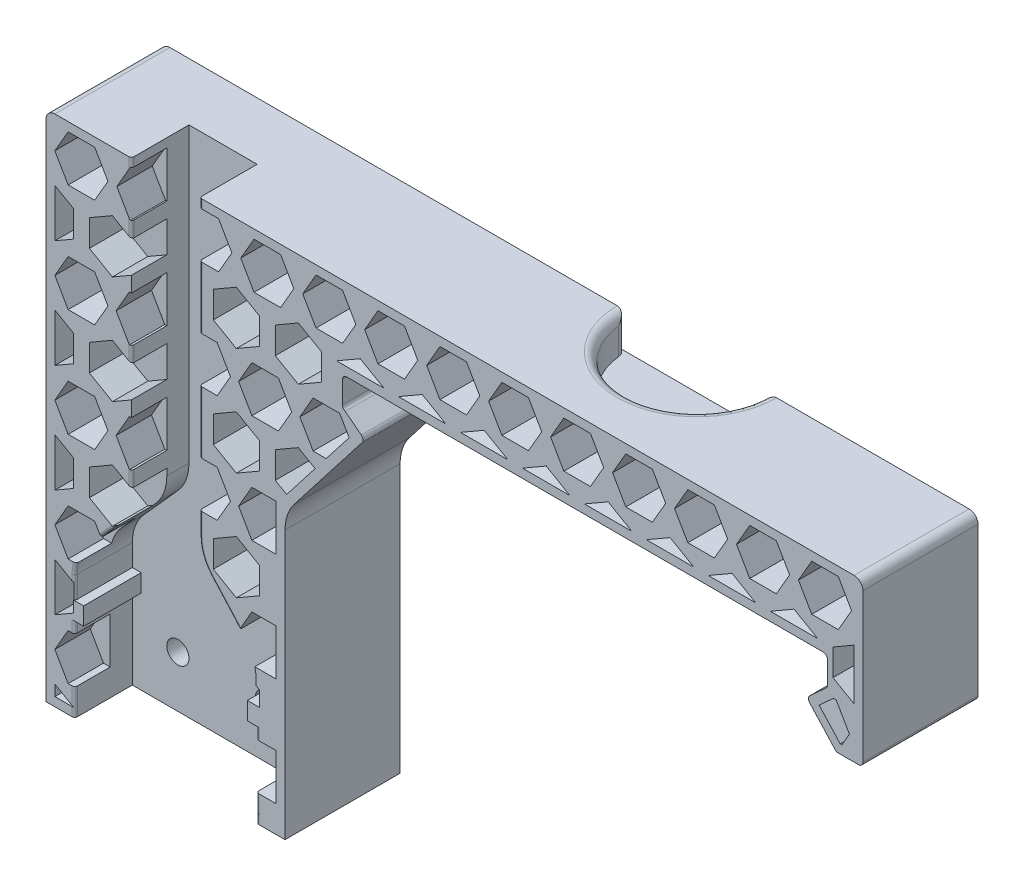
SolidWorks part; units mm, degrees
ref_plane "Front Plane" through (0, 0, 0) normal (0, 0, 1) x (1, 0, 0)
ref_plane "Top Plane" through (0, 0, 0) normal (0, 1, 0) x (1, 0, 0)
ref_plane "Right Plane" through (0, 0, 0) normal (1, 0, 0) x (0, 0, -1)
sketch "Sketch1" plane through (0, 0, 0) normal (0, 0, 1) x (1, 0, 0)
  line L0 (-19.1592, 3.1319) -> (34.6408, 3.1319)
  line L1 (-38.1408, 12.3758) -> (38.1408, 12.3758)
  line L4 (39.1408, 11.3758) -> (39.1408, -5.3957)
  line L5 (-53.1408, 0) -> (55.5927, 0) construction
  line L7 (35.1408, 2.6319) -> (35.1408, 0.1519)
  line L8 (34.9786, -0.2167) -> (33.1502, -1.8923)
  line L9 (-19.6592, 2.6319) -> (-19.6592, 0.1519)
  line L10 (-19.3447, -0.3124) -> (-17.527, -1.7246)
  line L12 (-17.1322, 5.631) -> (-17.1322, -19.9261) construction
  line L13 (-11.8322, 5.631) -> (-11.8322, -19.9261) construction
  line L14 (-19.6592, 23.1234) -> (-19.6592, -22.8153) construction
  line L16 (35.1408, 17.1234) -> (35.1408, -28.8153) construction
  line L17 (33.1194, -2.5987) -> (35.9922, -5.7336)
  line L18 (36.3608, -5.8957) -> (38.6408, -5.8957)
  line L19 (-17.4389, -2.4262) -> (-25.0892, -12.2733)
  line L20 (0, 22.1727) -> (0, -33.9968) construction
  line L21 (-85.6654, -9.6242) -> (72.0343, -9.6242) construction
  line L23 (-50.1408, -45.6242) -> (-26.1408, -45.6242)
  line L24 (-26.1408, -45.6242) -> (-26.1408, -15.3409)
  line L25 (-38.1408, 12.3758) -> (-52.1408, 12.3758)
  line L26 (-148.4921, -45.6242) -> (55.8577, -45.6242) construction
  line L27 (-53.1408, 11.3758) -> (-53.1408, -45.6242)
  line L28 (-53.1408, -45.6242) -> (-50.1408, -45.6242)
  line L30 (-39.6408, -25.8208) -> (-39.6408, -60.1482) construction
  arc A5 (-19.3447, -0.3124) -> (-19.6592, 0.1519) centre (-19.1592, 0.1519) cw
  arc A6 (35.1408, 0.1519) -> (34.9786, -0.2167) centre (34.6408, 0.1519) cw
  arc A7 (-19.1592, 3.1319) -> (-19.6592, 2.6319) centre (-19.1592, 2.6319) ccw
  arc A8 (35.1408, 2.6319) -> (34.6408, 3.1319) centre (34.6408, 2.6319) ccw
  arc A10 (38.6408, -5.8957) -> (39.1408, -5.3957) centre (38.6408, -5.3957) ccw
  arc A11 (36.3608, -5.8957) -> (35.9922, -5.7336) centre (36.3608, -5.3957) cw
  arc A12 (33.1194, -2.5987) -> (33.1502, -1.8923) centre (33.488, -2.2609) cw
  arc A13 (-17.4389, -2.4262) -> (-17.527, -1.7246) centre (-17.8338, -2.1194) ccw
  arc A14 (39.1408, 11.3758) -> (38.1408, 12.3758) centre (38.1408, 11.3758) ccw
  arc A15 (-52.1408, 12.3758) -> (-53.1408, 11.3758) centre (-52.1408, 11.3758) ccw
  arc A16 (-26.1408, -15.3409) -> (-25.0892, -12.2733) centre (-21.1408, -15.3409) cw
  point P0 (0, 0)
  point P1 (0, 12.3758)
  point P20 (-19.6592, -10.5)
  point P28 (-17.1322, -2.0313)
  point P29 (24.1408, -9.6242)
  point P33 (32.7816, -2.2301)
  point P36 (-19.6592, -0.0681)
  point P39 (35.1408, -0.0681)
  point P42 (-19.6592, 3.1319)
  point P45 (35.1408, 3.1319)
  point P49 (39.1408, -5.8957)
  point P52 (36.1408, -5.8957)
  point P55 (32.7816, -2.2301)
  point P58 (-17.1322, -2.0313)
  dimension "D8" = 90
  dimension "D13" = 3
  dimension "D15" = 90
  dimension "D16" = 4.9721
  dimension "D17" = 0.5
  dimension "D18" = 5.631
  dimension "D21" = 1
  dimension "D22" = 1
  dimension "D5" = 5
  dimension "D1" = 54.8
  dimension "D2" = 3.2
  dimension "D3" = 3.2
  dimension "D4" = 22
  dimension "D6" = 3.2
  dimension "D7" = 3.2
  dimension "D9" = 5.3
  dimension "D10" = 58
  dimension "D11" = 27
  dimension "D12" = 92.2816
  dimension "D14" = 4
  dimension "D19" = 19.9261
  dimension "D23" = 2.3018
extrude "Boss-Extrude1" add sketch "Sketch1" along normal mid plane 13
sketch "Sketch2" plane through (0, 0, 6.5) normal (0, 0, 1) x (1, 0, 0)
  line L0 (-53.1408, 11.3758) -> (-53.1408, -45.6242) construction
  line L1 (-49.1408, 18.485) -> (-49.1408, -51.4128) construction
  line L2 (-47.6408, -6.0165) -> (-46.1408, -3.4185)
  line L3 (-47.6408, 6.1796) -> (-46.1408, 8.7777)
  line L4 (-46.1408, 8.7777) -> (-47.6408, 11.3758)
  line L5 (-47.6408, 11.3758) -> (-50.6408, 11.3758)
  line L6 (-50.6408, 11.3758) -> (-52.1408, 8.7777)
  line L7 (-52.1408, 8.7777) -> (-50.6408, 6.1796)
  line L8 (-50.6408, 6.1796) -> (-47.6408, 6.1796)
  line L9 (38.1408, 12.3758) -> (-52.1408, 12.3758) construction
  line L10 (-40.6408, 6.1796) -> (-39.1408, 8.7777)
  line L11 (-39.1408, 8.7777) -> (-40.6408, 11.3758)
  line L12 (-40.6408, 11.3758) -> (-43.6408, 11.3758)
  line L13 (-43.6408, 11.3758) -> (-45.1408, 8.7777)
  line L14 (-45.1408, 8.7777) -> (-43.6408, 6.1796)
  line L15 (-43.6408, 6.1796) -> (-40.6408, 6.1796)
  line L16 (-33.6408, 6.1796) -> (-32.1408, 8.7777)
  line L17 (-32.1408, 8.7777) -> (-33.6408, 11.3758)
  line L18 (-33.6408, 11.3758) -> (-36.6408, 11.3758)
  line L19 (-36.6408, 11.3758) -> (-38.1408, 8.7777)
  line L20 (-38.1408, 8.7777) -> (-36.6408, 6.1796)
  line L21 (-36.6408, 6.1796) -> (-33.6408, 6.1796)
  line L22 (-26.6408, 6.1796) -> (-25.1408, 8.7777)
  line L23 (-25.1408, 8.7777) -> (-26.6408, 11.3758)
  line L24 (-26.6408, 11.3758) -> (-29.6408, 11.3758)
  line L25 (-29.6408, 11.3758) -> (-31.1408, 8.7777)
  line L26 (-31.1408, 8.7777) -> (-29.6408, 6.1796)
  line L27 (-29.6408, 6.1796) -> (-26.6408, 6.1796)
  line L28 (-19.6408, 6.1796) -> (-18.1408, 8.7777)
  line L29 (-18.1408, 8.7777) -> (-19.6408, 11.3758)
  line L30 (-19.6408, 11.3758) -> (-22.6408, 11.3758)
  line L31 (-22.6408, 11.3758) -> (-24.1408, 8.7777)
  line L32 (-24.1408, 8.7777) -> (-22.6408, 6.1796)
  line L33 (-22.6408, 6.1796) -> (-19.6408, 6.1796)
  line L34 (-12.6408, 6.1796) -> (-11.1408, 8.7777)
  line L35 (-11.1408, 8.7777) -> (-12.6408, 11.3758)
  line L36 (-12.6408, 11.3758) -> (-15.6408, 11.3758)
  line L37 (-15.6408, 11.3758) -> (-17.1408, 8.7777)
  line L38 (-17.1408, 8.7777) -> (-15.6408, 6.1796)
  line L39 (-15.6408, 6.1796) -> (-12.6408, 6.1796)
  line L40 (-5.6408, 6.1796) -> (-4.1408, 8.7777)
  line L41 (-4.1408, 8.7777) -> (-5.6408, 11.3758)
  line L42 (-5.6408, 11.3758) -> (-8.6408, 11.3758)
  line L43 (-8.6408, 11.3758) -> (-10.1408, 8.7777)
  line L44 (-10.1408, 8.7777) -> (-8.6408, 6.1796)
  line L45 (-8.6408, 6.1796) -> (-5.6408, 6.1796)
  line L46 (1.3592, 6.1796) -> (2.8592, 8.7777)
  line L47 (2.8592, 8.7777) -> (1.3592, 11.3758)
  line L48 (1.3592, 11.3758) -> (-1.6408, 11.3758)
  line L49 (-1.6408, 11.3758) -> (-3.1408, 8.7777)
  line L50 (-3.1408, 8.7777) -> (-1.6408, 6.1796)
  line L51 (-1.6408, 6.1796) -> (1.3592, 6.1796)
  line L52 (8.3592, 6.1796) -> (9.8592, 8.7777)
  line L53 (9.8592, 8.7777) -> (8.3592, 11.3758)
  line L54 (8.3592, 11.3758) -> (5.3592, 11.3758)
  line L55 (5.3592, 11.3758) -> (3.8592, 8.7777)
  line L56 (3.8592, 8.7777) -> (5.3592, 6.1796)
  line L57 (5.3592, 6.1796) -> (8.3592, 6.1796)
  line L58 (15.3592, 6.1796) -> (16.8592, 8.7777)
  line L59 (16.8592, 8.7777) -> (15.3592, 11.3758)
  line L60 (15.3592, 11.3758) -> (12.3592, 11.3758)
  line L61 (12.3592, 11.3758) -> (10.8592, 8.7777)
  line L62 (10.8592, 8.7777) -> (12.3592, 6.1796)
  line L63 (12.3592, 6.1796) -> (15.3592, 6.1796)
  line L64 (22.3592, 6.1796) -> (23.8592, 8.7777)
  line L65 (23.8592, 8.7777) -> (22.3592, 11.3758)
  line L66 (22.3592, 11.3758) -> (19.3592, 11.3758)
  line L67 (19.3592, 11.3758) -> (17.8592, 8.7777)
  line L68 (17.8592, 8.7777) -> (19.3592, 6.1796)
  line L69 (19.3592, 6.1796) -> (22.3592, 6.1796)
  line L70 (29.3592, 6.1796) -> (30.8592, 8.7777)
  line L71 (30.8592, 8.7777) -> (29.3592, 11.3758)
  line L72 (29.3592, 11.3758) -> (26.3592, 11.3758)
  line L73 (26.3592, 11.3758) -> (24.8592, 8.7777)
  line L74 (24.8592, 8.7777) -> (26.3592, 6.1796)
  line L75 (26.3592, 6.1796) -> (29.3592, 6.1796)
  line L76 (36.3592, 6.1796) -> (37.8592, 8.7777)
  line L77 (37.8592, 8.7777) -> (36.3592, 11.3758)
  line L78 (36.3592, 11.3758) -> (33.3592, 11.3758)
  line L79 (33.3592, 11.3758) -> (31.8592, 8.7777)
  line L80 (31.8592, 8.7777) -> (33.3592, 6.1796)
  line L81 (33.3592, 6.1796) -> (36.3592, 6.1796)
  line L82 (-53.1408, -45.6242) -> (-26.1408, -45.6242) construction
  line L83 (-45.6408, 13.774) -> (-45.6408, 5.8279) construction
  line L84 (-43.0427, 1.1796) -> (-43.0427, 4.1796)
  line L85 (-43.0427, 4.1796) -> (-45.6408, 5.6796)
  line L86 (-45.6408, 5.6796) -> (-48.2389, 4.1796)
  line L87 (-48.2389, 4.1796) -> (-48.2389, 1.1796)
  line L88 (-48.2389, 1.1796) -> (-45.6408, -0.3204)
  line L89 (-45.6408, -0.3204) -> (-43.0427, 1.1796)
  line L90 (-50.0427, 1.1796) -> (-50.0427, 4.1796)
  line L91 (-50.0427, 4.1796) -> (-52.1408, 5.3909)
  line L95 (-52.1408, -0.0317) -> (-50.0427, 1.1796)
  line L96 (-36.0427, 1.1796) -> (-36.0427, 4.1796)
  line L97 (-36.0427, 4.1796) -> (-38.6408, 5.6796)
  line L98 (-38.6408, 5.6796) -> (-41.2389, 4.1796)
  line L99 (-41.2389, 4.1796) -> (-41.2389, 1.1796)
  line L100 (-41.2389, 1.1796) -> (-38.6408, -0.3204)
  line L101 (-38.6408, -0.3204) -> (-36.0427, 1.1796)
  line L102 (-29.0427, 1.1796) -> (-29.0427, 4.1796)
  line L103 (-29.0427, 4.1796) -> (-31.6408, 5.6796)
  line L104 (-31.6408, 5.6796) -> (-34.2389, 4.1796)
  line L105 (-34.2389, 4.1796) -> (-34.2389, 1.1796)
  line L106 (-34.2389, 1.1796) -> (-31.6408, -0.3204)
  line L107 (-31.6408, -0.3204) -> (-29.0427, 1.1796)
  line L108 (-22.0427, 1.1796) -> (-22.0427, 4.1796)
  line L109 (-22.0427, 4.1796) -> (-24.6408, 5.6796)
  line L110 (-24.6408, 5.6796) -> (-27.2389, 4.1796)
  line L111 (-27.2389, 4.1796) -> (-27.2389, 1.1796)
  line L112 (-27.2389, 1.1796) -> (-24.6408, -0.3204)
  line L113 (-24.6408, -0.3204) -> (-22.0427, 1.1796)
  line L114 (-15.0427, 4.1319) -> (-15.0427, 4.1796)
  line L115 (-15.0427, 4.1796) -> (-17.6408, 5.6796)
  line L116 (-17.6408, 5.6796) -> (-20.2389, 4.1796)
  line L117 (-20.2389, 4.1796) -> (-20.2389, 4.1319)
  line L120 (-8.0427, 4.1319) -> (-8.0427, 4.1796)
  line L121 (-8.0427, 4.1796) -> (-10.6408, 5.6796)
  line L122 (-10.6408, 5.6796) -> (-13.2389, 4.1796)
  line L123 (-13.2389, 4.1796) -> (-13.2389, 4.1319)
  line L126 (-1.0427, 4.1319) -> (-1.0427, 4.1796)
  line L127 (-1.0427, 4.1796) -> (-3.6408, 5.6796)
  line L128 (-3.6408, 5.6796) -> (-6.2389, 4.1796)
  line L129 (-6.2389, 4.1796) -> (-6.2389, 4.1319)
  line L132 (5.9573, 4.1319) -> (5.9573, 4.1796)
  line L133 (5.9573, 4.1796) -> (3.3592, 5.6796)
  line L134 (3.3592, 5.6796) -> (0.7611, 4.1796)
  line L135 (0.7611, 4.1796) -> (0.7611, 4.1319)
  line L138 (12.9573, 4.1319) -> (12.9573, 4.1796)
  line L139 (12.9573, 4.1796) -> (10.3592, 5.6796)
  line L140 (10.3592, 5.6796) -> (7.7611, 4.1796)
  line L141 (7.7611, 4.1796) -> (7.7611, 4.1319)
  line L144 (19.9573, 4.1319) -> (19.9573, 4.1796)
  line L145 (19.9573, 4.1796) -> (17.3592, 5.6796)
  line L146 (17.3592, 5.6796) -> (14.7611, 4.1796)
  line L147 (14.7611, 4.1796) -> (14.7611, 4.1319)
  line L150 (26.9573, 4.1319) -> (26.9573, 4.1796)
  line L151 (26.9573, 4.1796) -> (24.3592, 5.6796)
  line L152 (24.3592, 5.6796) -> (21.7611, 4.1796)
  line L153 (21.7611, 4.1796) -> (21.7611, 4.1319)
  line L156 (33.9573, 4.1319) -> (33.9573, 4.1796)
  line L157 (33.9573, 4.1796) -> (31.3592, 5.6796)
  line L158 (31.3592, 5.6796) -> (28.7611, 4.1796)
  line L159 (28.7611, 4.1796) -> (28.7611, 4.1319)
  line L164 (38.1408, 5.5535) -> (35.7611, 4.1796)
  line L165 (35.7611, 4.1796) -> (35.7611, 1.1796)
  line L166 (35.7611, 1.1796) -> (38.1408, -0.1943)
  line L180 (-52.1408, 38.7076) -> (-52.1408, -77.5427) construction
  line L181 (-52.1408, 5.3909) -> (-52.1408, -0.0317)
  line L182 (38.1408, 32.9327) -> (38.1408, -35.597) construction
  line L183 (39.1408, -5.3957) -> (39.1408, 11.3758) construction
  line L184 (-52.6408, 5.6796) -> (-55.2389, 4.1796) [skipped]
  line L185 (-55.2389, 4.1796) -> (-55.2389, 1.1796) [skipped]
  line L186 (-55.2389, 1.1796) -> (-52.6408, -0.3204) [skipped]
  line L187 (38.1408, 5.5535) -> (38.1408, -0.1943)
  line L188 (47.9573, 1.1796) -> (47.9573, 4.1796) [skipped]
  line L189 (47.9573, 4.1796) -> (45.3592, 5.6796) [skipped]
  line L190 (45.3592, 5.6796) -> (42.7611, 4.1796) [skipped]
  line L191 (42.7611, 4.1796) -> (42.7611, 1.1796) [skipped]
  line L192 (42.7611, 1.1796) -> (45.3592, -0.3204) [skipped]
  line L193 (45.3592, -0.3204) -> (47.9573, 1.1796) [skipped]
  line L194 (54.9573, 1.1796) -> (54.9573, 4.1796) [skipped]
  line L195 (54.9573, 4.1796) -> (52.3592, 5.6796) [skipped]
  line L196 (52.3592, 5.6796) -> (49.7611, 4.1796) [skipped]
  line L197 (49.7611, 4.1796) -> (49.7611, 1.1796) [skipped]
  line L198 (49.7611, 1.1796) -> (52.3592, -0.3204) [skipped]
  line L199 (52.3592, -0.3204) -> (54.9573, 1.1796) [skipped]
  line L200 (-73.3307, 4.1319) -> (58.1866, 4.1319) construction
  line L201 (40.9573, 4.1796) -> (38.3592, 5.6796) [skipped]
  line L202 (40.9573, 1.1796) -> (40.9573, 4.1796) [skipped]
  line L203 (38.3592, -0.3204) -> (40.9573, 1.1796) [skipped]
  line L204 (-19.1592, 3.1319) -> (34.6408, 3.1319) construction
  line L205 (-20.2389, 4.1319) -> (-15.0427, 4.1319)
  line L206 (-13.2389, 4.1319) -> (-8.0427, 4.1319)
  line L207 (-6.2389, 4.1319) -> (-1.0427, 4.1319)
  line L208 (0.7611, 4.1319) -> (5.9573, 4.1319)
  line L209 (7.7611, 4.1319) -> (12.9573, 4.1319)
  line L210 (14.7611, 4.1319) -> (19.9573, 4.1319)
  line L211 (21.7611, 4.1319) -> (26.9573, 4.1319)
  line L212 (28.7611, 4.1319) -> (33.9573, 4.1319)
  line L213 (-46.1408, -3.4185) -> (-47.6408, -0.8204)
  line L214 (31.3592, -0.3204) -> (33.9573, 1.1796) [skipped]
  line L215 (28.7611, 1.1796) -> (31.3592, -0.3204) [skipped]
  line L216 (24.3592, -0.3204) -> (26.9573, 1.1796) [skipped]
  line L217 (21.7611, 1.1796) -> (24.3592, -0.3204) [skipped]
  line L218 (17.3592, -0.3204) -> (19.9573, 1.1796) [skipped]
  line L219 (14.7611, 1.1796) -> (17.3592, -0.3204) [skipped]
  line L220 (7.7611, 1.1796) -> (10.3592, -0.3204) [skipped]
  line L221 (10.3592, -0.3204) -> (12.9573, 1.1796) [skipped]
  line L222 (-20.2389, 1.1796) -> (-17.6408, -0.3204) [skipped]
  line L223 (-17.6408, -0.3204) -> (-15.0427, 1.1796) [skipped]
  line L224 (-10.6408, -0.3204) -> (-8.0427, 1.1796) [skipped]
  line L225 (-13.2389, 1.1796) -> (-10.6408, -0.3204) [skipped]
  line L226 (-3.6408, -0.3204) -> (-1.0427, 1.1796) [skipped]
  line L227 (-6.2389, 1.1796) -> (-3.6408, -0.3204) [skipped]
  line L228 (3.3592, -0.3204) -> (5.9573, 1.1796) [skipped]
  line L229 (0.7611, 1.1796) -> (3.3592, -0.3204) [skipped]
  line L230 (-47.6408, -0.8204) -> (-50.6408, -0.8204)
  line L231 (-50.6408, -0.8204) -> (-52.1408, -3.4185)
  line L232 (-52.1408, -3.4185) -> (-50.6408, -6.0165)
  line L233 (-50.6408, -6.0165) -> (-47.6408, -6.0165)
  line L234 (-40.7221, -6.0165) -> (-39.2221, -3.4185)
  line L235 (-39.2221, -3.4185) -> (-40.7221, -0.8204)
  line L236 (-40.7221, -0.8204) -> (-43.7221, -0.8204)
  line L237 (-43.7221, -0.8204) -> (-45.2221, -3.4185)
  line L238 (-45.2221, -3.4185) -> (-43.7221, -6.0165)
  line L239 (-43.7221, -6.0165) -> (-40.7221, -6.0165)
  line L240 (-33.8034, -6.0165) -> (-32.3034, -3.4185)
  line L241 (-32.3034, -3.4185) -> (-33.8034, -0.8204)
  line L242 (-33.8034, -0.8204) -> (-36.8034, -0.8204)
  line L243 (-36.8034, -0.8204) -> (-38.3034, -3.4185)
  line L244 (-38.3034, -3.4185) -> (-36.8034, -6.0165)
  line L245 (-36.8034, -6.0165) -> (-33.8034, -6.0165)
  line L246 (-26.8846, -6.0165) -> (-25.3846, -3.4185)
  line L247 (-25.3846, -3.4185) -> (-26.8846, -0.8204)
  line L248 (-26.8846, -0.8204) -> (-29.8846, -0.8204)
  line L249 (-29.8846, -0.8204) -> (-31.3846, -3.4185)
  line L250 (-31.3846, -3.4185) -> (-29.8846, -6.0165)
  line L251 (-29.8846, -6.0165) -> (-26.8846, -6.0165)
  line L253 (-18.8966, -2.6724) -> (-19.9659, -0.8204)
  line L254 (-19.9659, -0.8204) -> (-22.9659, -0.8204)
  line L255 (-22.9659, -0.8204) -> (-24.4659, -3.4185)
  line L256 (-24.4659, -3.4185) -> (-22.9659, -6.0165)
  line L257 (-22.9659, -6.0165) -> (-21.4946, -6.0165)
  line L258 (-21.4946, -6.0165) -> (-16.6539, 0.2142) construction
  line L259 (-25.0892, -12.2733) -> (-17.4389, -2.4262) construction
  line L260 (-21.4946, -6.0165) -> (-18.8966, -2.6724)
  line L261 (-52.1408, -12.2279) -> (-50.0427, -11.0165)
  line L263 (-19.9659, -6.0165) -> (-18.4659, -3.4185) [skipped]
  line L269 (-50.0427, -11.0165) -> (-50.0427, -8.0165)
  line L270 (-50.0427, -8.0165) -> (-52.1408, -6.8052)
  line L271 (-52.1408, -6.8052) -> (-52.1408, -12.2279)
  line L272 (-43.0427, -11.0165) -> (-43.0427, -8.0165)
  line L273 (-43.0427, -8.0165) -> (-45.6408, -6.5165)
  line L274 (-45.6408, -6.5165) -> (-48.2389, -8.0165)
  line L275 (-48.2389, -8.0165) -> (-48.2389, -11.0165)
  line L276 (-48.2389, -11.0165) -> (-45.6408, -12.5165)
  line L277 (-45.6408, -12.5165) -> (-43.0427, -11.0165)
  line L278 (-36.0427, -11.0165) -> (-36.0427, -8.0165)
  line L279 (-36.0427, -8.0165) -> (-38.6408, -6.5165)
  line L280 (-38.6408, -6.5165) -> (-41.2389, -8.0165)
  line L281 (-41.2389, -8.0165) -> (-41.2389, -11.0165)
  line L282 (-41.2389, -11.0165) -> (-38.6408, -12.5165)
  line L283 (-38.6408, -12.5165) -> (-36.0427, -11.0165)
  line L284 (-29.0427, -11.0165) -> (-29.0427, -8.0165)
  line L285 (-29.0427, -8.0165) -> (-31.6408, -6.5165)
  line L286 (-31.6408, -6.5165) -> (-34.2389, -8.0165)
  line L287 (-34.2389, -8.0165) -> (-34.2389, -11.0165)
  line L288 (-34.2389, -11.0165) -> (-31.6408, -12.5165)
  line L289 (-31.6408, -12.5165) -> (-29.0427, -11.0165)
  line L291 (-22.737, -7.6157) -> (-24.6408, -6.5165)
  line L292 (-24.6408, -6.5165) -> (-27.2389, -8.0165)
  line L293 (-27.2389, -8.0165) -> (-27.2389, -11.0165)
  line L294 (-27.2389, -11.0165) -> (-25.955, -11.7578)
  line L296 (-21.4946, -6.0165) -> (-26.8846, -12.9543) construction
  line L297 (-25.955, -11.7578) -> (-22.737, -7.6157)
  line L298 (-47.6408, -18.2127) -> (-46.1408, -15.6146)
  line L299 (-46.1408, -15.6146) -> (-47.6408, -13.0165)
  line L300 (-22.0427, -11.0165) -> (-22.0427, -8.0165) [skipped]
  line L301 (-24.6408, -12.5165) -> (-22.0427, -11.0165) [skipped]
  line L302 (-47.6408, -13.0165) -> (-50.6408, -13.0165)
  line L303 (-50.6408, -13.0165) -> (-52.1408, -15.6146)
  line L304 (-52.1408, -15.6146) -> (-50.6408, -18.2127)
  line L305 (-50.6408, -18.2127) -> (-47.6408, -18.2127)
  line L306 (-40.7221, -18.2127) -> (-39.2221, -15.6146)
  line L307 (-39.2221, -15.6146) -> (-40.7221, -13.0165)
  line L308 (-40.7221, -13.0165) -> (-43.7221, -13.0165)
  line L309 (-43.7221, -13.0165) -> (-45.2221, -15.6146)
  line L310 (-45.2221, -15.6146) -> (-43.7221, -18.2127)
  line L311 (-43.7221, -18.2127) -> (-40.7221, -18.2127)
  line L312 (-33.8034, -18.2127) -> (-32.3034, -15.6146)
  line L313 (-32.3034, -15.6146) -> (-33.8034, -13.0165)
  line L314 (-33.8034, -13.0165) -> (-36.8034, -13.0165)
  line L315 (-36.8034, -13.0165) -> (-38.3034, -15.6146)
  line L316 (-38.3034, -15.6146) -> (-36.8034, -18.2127)
  line L317 (-36.8034, -18.2127) -> (-33.8034, -18.2127)
  line L320 (-27.1408, -13.0165) -> (-29.8846, -13.0165)
  line L321 (-29.8846, -13.0165) -> (-31.3846, -15.6146)
  line L322 (-31.3846, -15.6146) -> (-29.8846, -18.2127)
  line L323 (-29.8846, -18.2127) -> (-27.1408, -18.2127)
  line L324 (-27.1408, -53.2478) -> (-27.1408, 20.1443) construction
  line L325 (-26.1408, -45.6242) -> (-26.1408, -15.3409) construction
  line L326 (-27.1408, -18.2127) -> (-27.1408, -13.0165)
  line L327 (-52.1408, -24.424) -> (-50.0427, -23.2127)
  line L328 (-50.0427, -23.2127) -> (-50.0427, -20.2127)
  line L329 (-25.3846, -15.6146) -> (-26.8846, -13.0165) [skipped]
  line L330 (-26.8846, -18.2127) -> (-25.3846, -15.6146) [skipped]
  line L331 (-50.0427, -20.2127) -> (-52.1408, -19.0014)
  line L332 (-52.1408, -19.0014) -> (-52.1408, -24.424)
  line L333 (-43.0427, -23.2127) -> (-43.0427, -20.2127)
  line L334 (-43.0427, -20.2127) -> (-45.6408, -18.7127)
  line L335 (-45.6408, -18.7127) -> (-48.2389, -20.2127)
  line L336 (-48.2389, -20.2127) -> (-48.2389, -23.2127)
  line L337 (-48.2389, -23.2127) -> (-45.6408, -24.7127)
  line L338 (-45.6408, -24.7127) -> (-43.0427, -23.2127)
  line L339 (-36.0427, -23.2127) -> (-36.0427, -20.2127)
  line L340 (-36.0427, -20.2127) -> (-38.6408, -18.7127)
  line L341 (-38.6408, -18.7127) -> (-41.2389, -20.2127)
  line L342 (-41.2389, -20.2127) -> (-41.2389, -23.2127)
  line L343 (-41.2389, -23.2127) -> (-38.6408, -24.7127)
  line L344 (-38.6408, -24.7127) -> (-36.0427, -23.2127)
  line L345 (-29.0427, -23.2127) -> (-29.0427, -20.2127)
  line L346 (-29.0427, -20.2127) -> (-31.6408, -18.7127)
  line L347 (-31.6408, -18.7127) -> (-34.2389, -20.2127)
  line L348 (-34.2389, -20.2127) -> (-34.2389, -23.2127)
  line L349 (-34.2389, -23.2127) -> (-31.6408, -24.7127)
  line L350 (-31.6408, -24.7127) -> (-29.0427, -23.2127)
  line L351 (-47.6408, -30.4088) -> (-46.1408, -27.8108)
  line L352 (-46.1408, -27.8108) -> (-47.6408, -25.2127)
  line L353 (-47.6408, -25.2127) -> (-50.6408, -25.2127)
  line L354 (-50.6408, -25.2127) -> (-52.1408, -27.8108)
  line L355 (-52.1408, -27.8108) -> (-50.6408, -30.4088)
  line L356 (-50.6408, -30.4088) -> (-47.6408, -30.4088)
  line L357 (-40.7221, -30.4088) -> (-39.2221, -27.8108)
  line L358 (-39.2221, -27.8108) -> (-40.7221, -25.2127)
  line L359 (-40.7221, -25.2127) -> (-43.7221, -25.2127)
  line L360 (-43.7221, -25.2127) -> (-45.2221, -27.8108)
  line L361 (-45.2221, -27.8108) -> (-43.7221, -30.4088)
  line L362 (-43.7221, -30.4088) -> (-40.7221, -30.4088)
  line L363 (-33.8034, -30.4088) -> (-32.3034, -27.8108)
  line L364 (-32.3034, -27.8108) -> (-33.8034, -25.2127)
  line L365 (-33.8034, -25.2127) -> (-36.8034, -25.2127)
  line L366 (-36.8034, -25.2127) -> (-38.3034, -27.8108)
  line L367 (-38.3034, -27.8108) -> (-36.8034, -30.4088)
  line L368 (-36.8034, -30.4088) -> (-33.8034, -30.4088)
  line L369 (-31.3846, -27.8108) -> (-29.8846, -30.4088)
  line L370 (-29.8846, -30.4088) -> (-27.1408, -30.4088)
  line L371 (-27.1408, -30.4088) -> (-27.1408, -25.2127)
  line L372 (-27.1408, -25.2127) -> (-29.8846, -25.2127)
  line L373 (-29.8846, -25.2127) -> (-31.3846, -27.8108)
  line L374 (-52.1408, -36.6202) -> (-50.0427, -35.4088)
  line L375 (-50.0427, -35.4088) -> (-50.0427, -32.4088)
  line L376 (-50.0427, -32.4088) -> (-52.1408, -31.1975)
  line L377 (-52.1408, -31.1975) -> (-52.1408, -36.6202)
  line L378 (-43.0427, -35.4088) -> (-43.0427, -32.4088)
  line L379 (-43.0427, -32.4088) -> (-45.6408, -30.9088)
  line L380 (-45.6408, -30.9088) -> (-48.2389, -32.4088)
  line L381 (-48.2389, -32.4088) -> (-48.2389, -35.4088)
  line L382 (-48.2389, -35.4088) -> (-45.6408, -36.9088)
  line L383 (-45.6408, -36.9088) -> (-43.0427, -35.4088)
  line L384 (-36.0427, -35.4088) -> (-36.0427, -32.4088)
  line L385 (-36.0427, -32.4088) -> (-38.6408, -30.9088)
  line L386 (-38.6408, -30.9088) -> (-41.2389, -32.4088)
  line L387 (-41.2389, -32.4088) -> (-41.2389, -35.4088)
  line L388 (-41.2389, -35.4088) -> (-38.6408, -36.9088)
  line L389 (-38.6408, -36.9088) -> (-36.0427, -35.4088)
  line L390 (-29.0427, -35.4088) -> (-29.0427, -32.4088)
  line L391 (-29.0427, -32.4088) -> (-31.6408, -30.9088)
  line L392 (-31.6408, -30.9088) -> (-34.2389, -32.4088)
  line L393 (-34.2389, -32.4088) -> (-34.2389, -35.4088)
  line L394 (-34.2389, -35.4088) -> (-31.6408, -36.9088)
  line L395 (-31.6408, -36.9088) -> (-29.0427, -35.4088)
  line L396 (-47.6408, -42.605) -> (-46.1408, -40.0069)
  line L397 (-46.1408, -40.0069) -> (-47.6408, -37.4088)
  line L398 (-47.6408, -37.4088) -> (-50.6408, -37.4088)
  line L399 (-50.6408, -37.4088) -> (-52.1408, -40.0069)
  line L400 (-52.1408, -40.0069) -> (-50.6408, -42.605)
  line L401 (-50.6408, -42.605) -> (-47.6408, -42.605)
  line L402 (-40.7221, -42.605) -> (-39.2221, -40.0069)
  line L403 (-39.2221, -40.0069) -> (-40.7221, -37.4088)
  line L404 (-40.7221, -37.4088) -> (-43.7221, -37.4088)
  line L405 (-43.7221, -37.4088) -> (-45.2221, -40.0069)
  line L406 (-45.2221, -40.0069) -> (-43.7221, -42.605)
  line L407 (-43.7221, -42.605) -> (-40.7221, -42.605)
  line L408 (-33.8034, -42.605) -> (-32.3034, -40.0069)
  line L409 (-32.3034, -40.0069) -> (-33.8034, -37.4088)
  line L410 (-33.8034, -37.4088) -> (-36.8034, -37.4088)
  line L411 (-36.8034, -37.4088) -> (-38.3034, -40.0069)
  line L412 (-38.3034, -40.0069) -> (-36.8034, -42.605)
  line L413 (-36.8034, -42.605) -> (-33.8034, -42.605)
  line L414 (-31.3846, -40.0069) -> (-29.8846, -42.605)
  line L415 (-29.8846, -42.605) -> (-27.1408, -42.605)
  line L416 (-27.1408, -42.605) -> (-27.1408, -37.4088)
  line L417 (-27.1408, -37.4088) -> (-29.8846, -37.4088)
  line L418 (-29.8846, -37.4088) -> (-31.3846, -40.0069)
  line L420 (-50.0427, -44.6242) -> (-50.0427, -44.605)
  line L421 (-50.0427, -44.605) -> (-52.1408, -43.3937)
  line L422 (-52.1408, -43.3937) -> (-52.1408, -44.6242)
  line L423 (-43.0427, -44.6242) -> (-43.0427, -44.605)
  line L424 (-43.0427, -44.605) -> (-45.6408, -43.105)
  line L425 (-45.6408, -43.105) -> (-48.2389, -44.605)
  line L426 (-48.2389, -44.605) -> (-48.2389, -44.6242)
  line L429 (-36.0427, -44.6242) -> (-36.0427, -44.605)
  line L430 (-36.0427, -44.605) -> (-38.6408, -43.105)
  line L431 (-38.6408, -43.105) -> (-41.2389, -44.605)
  line L432 (-41.2389, -44.605) -> (-41.2389, -44.6242)
  line L435 (-29.0427, -44.6242) -> (-29.0427, -44.605)
  line L436 (-29.0427, -44.605) -> (-31.6408, -43.105)
  line L437 (-31.6408, -43.105) -> (-34.2389, -44.605)
  line L438 (-34.2389, -44.605) -> (-34.2389, -44.6242)
  line L489 (36.7625, -4.8957) -> (37.6154, -3.4185)
  line L490 (37.6154, -3.4185) -> (36.1154, -0.8204)
  line L491 (36.1154, -0.8204) -> (35.8, -0.8204)
  line L492 (33.1154, -0.8204) -> (33.0113, -1.0006)
  line L525 (-19.8846, -6.0165) -> (-18.3846, -3.4185) [skipped]
  line L526 (-18.3846, -3.4185) -> (-19.8846, -0.8204) [skipped]
  line L527 (-19.8846, -0.8204) -> (-22.8846, -0.8204) [skipped]
  line L528 (-22.8846, -0.8204) -> (-24.3846, -3.4185) [skipped]
  line L529 (-24.3846, -3.4185) -> (-22.8846, -6.0165) [skipped]
  line L530 (-22.8846, -6.0165) -> (-19.8846, -6.0165) [skipped]
  line L531 (-12.8846, -6.0165) -> (-11.3846, -3.4185) [skipped]
  line L532 (-11.3846, -3.4185) -> (-12.8846, -0.8204) [skipped]
  line L533 (-12.8846, -0.8204) -> (-15.8846, -0.8204) [skipped]
  line L534 (-15.8846, -0.8204) -> (-17.3846, -3.4185) [skipped]
  line L535 (-17.3846, -3.4185) -> (-15.8846, -6.0165) [skipped]
  line L536 (-15.8846, -6.0165) -> (-12.8846, -6.0165) [skipped]
  line L537 (-5.8846, -6.0165) -> (-4.3846, -3.4185) [skipped]
  line L538 (-4.3846, -3.4185) -> (-5.8846, -0.8204) [skipped]
  line L539 (-5.8846, -0.8204) -> (-8.8846, -0.8204) [skipped]
  line L540 (-8.8846, -0.8204) -> (-10.3846, -3.4185) [skipped]
  line L541 (-10.3846, -3.4185) -> (-8.8846, -6.0165) [skipped]
  line L542 (-8.8846, -6.0165) -> (-5.8846, -6.0165) [skipped]
  line L543 (1.1154, -6.0165) -> (2.6154, -3.4185) [skipped]
  line L544 (2.6154, -3.4185) -> (1.1154, -0.8204) [skipped]
  line L545 (1.1154, -0.8204) -> (-1.8846, -0.8204) [skipped]
  line L546 (-1.8846, -0.8204) -> (-3.3846, -3.4185) [skipped]
  line L547 (-3.3846, -3.4185) -> (-1.8846, -6.0165) [skipped]
  line L548 (-1.8846, -6.0165) -> (1.1154, -6.0165) [skipped]
  line L549 (8.1154, -6.0165) -> (9.6154, -3.4185) [skipped]
  line L550 (9.6154, -3.4185) -> (8.1154, -0.8204) [skipped]
  line L551 (8.1154, -0.8204) -> (5.1154, -0.8204) [skipped]
  line L552 (5.1154, -0.8204) -> (3.6154, -3.4185) [skipped]
  line L553 (3.6154, -3.4185) -> (5.1154, -6.0165) [skipped]
  line L554 (5.1154, -6.0165) -> (8.1154, -6.0165) [skipped]
  line L555 (15.1154, -6.0165) -> (16.6154, -3.4185) [skipped]
  line L556 (16.6154, -3.4185) -> (15.1154, -0.8204) [skipped]
  line L557 (15.1154, -0.8204) -> (12.1154, -0.8204) [skipped]
  line L558 (12.1154, -0.8204) -> (10.6154, -3.4185) [skipped]
  line L559 (10.6154, -3.4185) -> (12.1154, -6.0165) [skipped]
  line L560 (12.1154, -6.0165) -> (15.1154, -6.0165) [skipped]
  line L561 (22.1154, -6.0165) -> (23.6154, -3.4185) [skipped]
  line L562 (23.6154, -3.4185) -> (22.1154, -0.8204) [skipped]
  line L563 (22.1154, -0.8204) -> (19.1154, -0.8204) [skipped]
  line L564 (19.1154, -0.8204) -> (17.6154, -3.4185) [skipped]
  line L565 (17.6154, -3.4185) -> (19.1154, -6.0165) [skipped]
  line L566 (19.1154, -6.0165) -> (22.1154, -6.0165) [skipped]
  line L567 (29.1154, -6.0165) -> (30.6154, -3.4185) [skipped]
  line L568 (30.6154, -3.4185) -> (29.1154, -0.8204) [skipped]
  line L569 (29.1154, -0.8204) -> (26.1154, -0.8204) [skipped]
  line L570 (26.1154, -0.8204) -> (24.6154, -3.4185) [skipped]
  line L571 (24.6154, -3.4185) -> (26.1154, -6.0165) [skipped]
  line L572 (26.1154, -6.0165) -> (29.1154, -6.0165) [skipped]
  line L573 (43.1154, -6.0165) -> (44.6154, -3.4185) [skipped]
  line L574 (44.6154, -3.4185) -> (43.1154, -0.8204) [skipped]
  line L575 (43.1154, -0.8204) -> (40.1154, -0.8204) [skipped]
  line L576 (40.1154, -6.0165) -> (43.1154, -6.0165) [skipped]
  line L577 (50.1154, -6.0165) -> (51.6154, -3.4185) [skipped]
  line L578 (51.6154, -3.4185) -> (50.1154, -0.8204) [skipped]
  line L579 (50.1154, -0.8204) -> (47.1154, -0.8204) [skipped]
  line L580 (47.1154, -0.8204) -> (45.6154, -3.4185) [skipped]
  line L581 (45.6154, -3.4185) -> (47.1154, -6.0165) [skipped]
  line L582 (47.1154, -6.0165) -> (50.1154, -6.0165) [skipped]
  line L583 (57.1154, -6.0165) -> (58.6154, -3.4185) [skipped]
  line L584 (58.6154, -3.4185) -> (57.1154, -0.8204) [skipped]
  line L585 (57.1154, -0.8204) -> (54.1154, -0.8204) [skipped]
  line L586 (54.1154, -0.8204) -> (52.6154, -3.4185) [skipped]
  line L587 (52.6154, -3.4185) -> (54.1154, -6.0165) [skipped]
  line L588 (54.1154, -6.0165) -> (57.1154, -6.0165) [skipped]
  line L589 (64.1154, -6.0165) -> (65.6154, -3.4185) [skipped]
  line L590 (65.6154, -3.4185) -> (64.1154, -0.8204) [skipped]
  line L591 (64.1154, -0.8204) -> (61.1154, -0.8204) [skipped]
  line L592 (61.1154, -0.8204) -> (59.6154, -3.4185) [skipped]
  line L593 (59.6154, -3.4185) -> (61.1154, -6.0165) [skipped]
  line L594 (61.1154, -6.0165) -> (64.1154, -6.0165) [skipped]
  line L595 (71.1154, -6.0165) -> (72.6154, -3.4185) [skipped]
  line L596 (72.6154, -3.4185) -> (71.1154, -0.8204) [skipped]
  line L597 (71.1154, -0.8204) -> (68.1154, -0.8204) [skipped]
  line L598 (68.1154, -0.8204) -> (66.6154, -3.4185) [skipped]
  line L599 (66.6154, -3.4185) -> (68.1154, -6.0165) [skipped]
  line L600 (68.1154, -6.0165) -> (71.1154, -6.0165) [skipped]
  line L601 (40.1154, -0.8204) -> (38.6154, -3.4185) [skipped]
  line L602 (38.6154, -3.4185) -> (40.1154, -6.0165) [skipped]
  line L603 (40.8977, -4.8957) -> (30.4594, -4.8957) construction
  line L604 (36.3608, -5.8957) -> (38.6408, -5.8957) construction
  line L605 (37.8603, -6.292) -> (31.3969, 0.7611) construction
  line L606 (33.1194, -2.5987) -> (35.9922, -5.7336) construction
  line L607 (29.9378, -6.1925) -> (40.0047, 3.0328) construction
  line L608 (34.9786, -0.2167) -> (33.1502, -1.8923) construction
  line L609 (35.8, -0.8204) -> (34.1945, -2.2917)
  line L610 (34.1945, -2.2917) -> (36.5808, -4.8957)
  line L611 (36.5808, -4.8957) -> (36.7625, -4.8957)
  line L612 (-58.095, -44.6242) -> (-15.0427, -44.6242) construction
  line L613 (-52.1408, -44.6242) -> (-50.0427, -44.6242)
  line L614 (33.1154, -6.0165) -> (36.1154, -6.0165) [skipped]
  line L615 (32.0823, -4.2273) -> (32.4683, -4.8957) [skipped]
  line L616 (-48.2389, -44.6242) -> (-43.0427, -44.6242)
  line L617 (-41.2389, -44.6242) -> (-36.0427, -44.6242)
  line L618 (-34.2389, -44.6242) -> (-29.0427, -44.6242)
  line L621 (-52.1408, -48.8163) -> (-50.0427, -47.605) [skipped]
  line L622 (-48.2389, -47.605) -> (-45.6408, -49.105) [skipped]
  line L623 (-45.6408, -49.105) -> (-43.0427, -47.605) [skipped]
  line L624 (-41.2389, -47.605) -> (-38.6408, -49.105) [skipped]
  line L625 (-38.6408, -49.105) -> (-36.0427, -47.605) [skipped]
  line L626 (-34.2389, -47.605) -> (-31.6408, -49.105) [skipped]
  line L627 (-31.6408, -49.105) -> (-29.0427, -47.605) [skipped]
  circle A0 centre (-49.1408, 8.7777) radius 2.5981 construction
  circle A1 centre (-45.6408, 2.6796) radius 2.5981 construction
  circle A2 centre (-49.1408, -3.4185) radius 2.5981 construction
  dimension "D1" = 3
  dimension "D2" = 1
  dimension "D3" = 1
  dimension "D5" = 8
  dimension "D6" = 3
  dimension "D7" = 0.5
  dimension "D8" = 2
  dimension "D9" = 15
  dimension "D10" = 1
  dimension "D11" = 1
  dimension "D12" = 3
  dimension "D13" = 5
  dimension "D14" = 1
  dimension "D15" = 0.5
  dimension "D16" = 27
  dimension "D17" = 2
  dimension "D18" = 0.5
  dimension "D19" = 2
  dimension "D20" = 0.5
  dimension "D21" = 1
  dimension "D22" = 2
  dimension "D23" = 0.5
  dimension "D24" = 2
  dimension "D25" = 0.5
  dimension "D26" = 2
  dimension "D27" = 0.5
  dimension "D28" = 2
  dimension "D29" = 0.5
  dimension "D30" = 15
  dimension "D31" = 1
  dimension "D32" = 1
  dimension "D33" = 1
  dimension "D34" = 1
  dimension "D4" = 13
sketch "Sketch3" plane through (0, 0, 6.5) normal (0, 0, 1) x (1, 0, 0)
  line L0 (-39.6408, 20.3143) -> (-39.6408, -57.9748) construction
  line L1 (-53.1408, 11.3758) -> (-53.1408, -45.6242) construction
  line L2 (-26.1408, -45.6242) -> (-26.1408, -15.3409) construction
  line L3 (-49.8908, -45.6242) -> (-49.8908, -31.6784)
  line L4 (-53.1408, -45.6242) -> (-26.1408, -45.6242) construction
  line L5 (-49.8908, -45.6242) -> (-29.3908, -45.6242)
  line L6 (-29.3908, -31.6784) -> (-29.3908, -45.6242)
  line L13 (-70.0343, -36.1242) -> (9.4179, -36.1242) construction
  line L14 (-29.3908, -36.1242) -> (-30.3908, -36.1242)
  line L15 (-30.3908, -36.1242) -> (-30.3908, -34.1242)
  line L16 (-30.3908, -34.1242) -> (-29.3908, -34.1242)
  line L17 (-48.8908, -34.1242) -> (-49.8908, -34.1242)
  line L18 (-48.8908, -36.1242) -> (-48.8908, -34.1242)
  line L19 (-49.8908, -36.1242) -> (-48.8908, -36.1242)
  line L20 (-70.0343, -39.8242) -> (9.4179, -39.8242) construction
  line L21 (-33.4908, -37.5972) -> (-33.4908, -49.5122) construction
  line L22 (-35.9908, -37.5972) -> (-35.9908, -49.5122) construction
  line L23 (-43.4908, -37.5972) -> (-43.4908, -49.5122) construction
  line L24 (-43.4908, 12.3758) -> (-43.4908, -20.7116)
  line L25 (38.1408, 12.3758) -> (-52.1408, 12.3758) construction
  line L26 (-35.7908, 12.3758) -> (-35.7908, -20.7116)
  line L27 (-48.6144, -28.3414) -> (-44.7672, -24.0486)
  line L28 (-34.5144, -24.0486) -> (-30.6672, -28.3414)
  circle A4 centre (-34.7408, -39.8242) radius 1.25
  circle A5 centre (-44.7408, -39.8242) radius 1.25
  arc A6 (-29.3908, -31.6784) -> (-30.6672, -28.3414) centre (-34.3908, -31.6784) ccw
  arc A7 (-48.6144, -28.3414) -> (-49.8908, -31.6784) centre (-44.8908, -31.6784) ccw
  arc A8 (-35.7908, -20.7116) -> (-34.5144, -24.0486) centre (-30.7908, -20.7116) ccw
  arc A9 (-43.4908, -20.7116) -> (-44.7672, -24.0486) centre (-48.4908, -20.7116) cw
  point P20 (-29.3908, -23.6242)
  point P23 (-50.0908, -23.6242)
  point P28 (-42.1408, -5.6242)
  point P51 (-43.4908, -22.6242)
  point P52 (-79.0258, -32.9092)
  point P53 (-104.5633, -14.5905)
  dimension "D6" = 20.5
  dimension "D12" = 2.5
  dimension "D14" = 2.5
  dimension "D4" = 5
  dimension "D2" = 22
  dimension "D3" = 35
  dimension "D7" = 9.5
  dimension "D8" = 1
  dimension "D9" = 2
  dimension "D10" = 5.8
  dimension "D11" = 4.1
  dimension "D13" = 7.5
extrude "Cut-Extrude1" cut sketch "Sketch3" against normal blind 6.5
sketch "Sketch4" plane through (0, 0, 6.5) normal (0, 0, 1) x (1, 0, 0)
  circle A0 centre (-44.7408, -39.8242) radius 1
  circle A1 centre (-34.7408, -39.8242) radius 1
extrude "Cut-Extrude4" cut sketch "Sketch2" against normal blind 4 contours L438 L618 L435 L436 L437 | L432 L617 L429 L430 L431 | L426 L616 L423 L424 L425 | L422 L613 L420 L421 | L400 L401 L396 L397 L398 L399 | L406 L407 L402 L403 L404 L405 | L412 L413 L408 L409 L410 L411 | L417 L418 L414 L415 L416 | L394 L395 L390 L391 L392 L393 | L388 L389 L384 L385 L386 L387 | L382 L383 L378 L379 L380 L381 | L376 L377 L374 L375 | L355 L356 L351 L352 L353 L354 | L361 L362 L357 L358 L359 L360 | L367 L368 L363 L364 L365 L366 | L372 L373 L369 L370 L371 | L349 L350 L345 L346 L347 L348 | L343 L344 L339 L340 L341 L342 | L337 L338 L333 L334 L335 L336 | L331 L332 L327 L328 | L323 L326 L320 L321 L322 | L294 L297 L291 L292 L293 | L257 L260 L253 L254 L255 L256 | L250 L251 L246 L247 L248 L249 | L288 L289 L284 L285 L286 L287 | L316 L317 L312 L313 L314 L315 | L310 L311 L306 L307 L308 L309 | L282 L283 L278 L279 L280 L281 | L244 L245 L240 L241 L242 L243 | L238 L239 L234 L235 L236 L237 | L276 L277 L272 L273 L274 L275 | L270 L271 L261 L269 | L232 L233 L2 L213 L230 L231 | L304 L305 L298 L299 L302 L303 | L610 L611 L489 L490 L491 L609 | L187 L164 L165 L166 | L80 L81 L76 L77 L78 L79 | L74 L75 L70 L71 L72 L73 | L68 L69 L64 L65 L66 L67 | L62 L63 L58 L59 L60 L61 | L56 L57 L52 L53 L54 L55 | L50 L51 L46 L47 L48 L49 | L44 L45 L40 L41 L42 L43 | L38 L39 L34 L35 L36 L37 | L32 L33 L28 L29 L30 L31 | L112 L113 L108 L109 L110 L111 | L106 L107 L102 L103 L104 L105 | L26 L27 L22 L23 L24 L25 | L20 L21 L16 L17 L18 L19 | L100 L101 L96 L97 L98 L99 | L88 L89 L84 L85 L86 L87 | L14 L15 L10 L11 L12 L13 | L7 L8 L3 L4 L5 L6 | L91 L181 L95 L90 | L117 L205 L114 L115 L116 | L123 L206 L120 L121 L122 | L129 L207 L126 L127 L128 | L135 L208 L132 L133 L134 | L141 L209 L138 L139 L140 | L159 L212 L156 L157 L158 | L153 L211 L150 L151 L152 | L147 L210 L144 L145 L146
sketch "Sketch5" plane through (0, 0, 2.5) normal (0, 0, 1) x (1, 0, 0)
  line L0 (-29.5908, -34.1242) -> (-29.0427, -34.1242)
  line L1 (-30.3908, -34.1242) -> (-29.5908, -34.1242)
  line L2 (-30.3908, -34.1242) -> (-30.3908, -36.1242)
  line L3 (-30.3908, -36.1242) -> (-29.3908, -36.1242)
  line L5 (-29.0427, -35.4088) -> (-29.0427, -32.4088) construction
  line L6 (-29.0427, -34.1242) -> (-29.0427, -36.1242)
  line L7 (-29.0427, -36.1242) -> (-29.3908, -36.1242)
extrude "Boss-Extrude2" add sketch "Sketch5" along normal up to surface (4 mm away) up to face at (-29.0871, -15.6146, 6.5)
sketch "Sketch6" plane through (0, 12.3758, 0) normal (0, 1, 0) x (1, 0, 0)
  line L0 (7.3947, -6.5) -> (7.3947, 6.5) construction
  line L1 (38.1408, -6.5) -> (-35.7908, -6.5) construction
  line L2 (38.1408, 6.5) -> (-52.1408, 6.5) construction
  line L3 (-0.6053, 6.5) -> (15.3947, 6.5)
  arc A0 (-0.6053, 6.5) -> (15.3947, 6.5) centre (7.3947, 6.5) ccw
  dimension "D1" = 16
extrude "Cut-Extrude5" cut sketch "Sketch6" against normal blind 4
fillet "Fillet3" radius 1 3 edges at (15.3947, 10.3758, -6.5) (-0.6053, 10.3758, -6.5) (7.3947, 12.3758, 1.5)
fillet "Fillet5" radius 0.3 18 edges at (-49.8497, -31.0383, 6.5) (-49.8908, -44.1146, 6.5) (-49.8908, -36.7665, 6.5) (-49.8908, -32.9013, 6.5) (-45.9938, -25.4172, 6.5) (-43.4908, -19.0833, 6.5) (-43.4908, -6.8872, 6.5) (-43.4908, 5.309, 6.5) (-43.4908, 11.8758, 6.5) (-35.7908, 11.8758, 6.5) (-35.7908, 2.6796, 6.5) (-35.7908, -9.5165, 6.5) (-35.7908, -19.4622, 6.5) (-29.3908, -43.5045, 6.5) (-29.3908, -45.1242, 6.5) (-29.3908, -36.7665, 6.5) (-32.9021, -25.8476, 6.5) (-35.4608, -22.498, 6.5)
sketch "Sketch7" plane through (0, 0, 6.5) normal (0, 0, 1) x (1, 0, 0)
  circle A0 centre (-44.7408, -39.8242) radius 1.25
  circle A1 centre (-34.7408, -39.8242) radius 1.25
extrude "Cut-Extrude6" cut sketch "Sketch7" against normal blind 10
sketch "Sketch8" plane through (0, 0, -3.5) normal (0, 0, 1) x (1, 0, 0)
  circle A0 centre (-34.7408, -39.8242) radius 1.25
